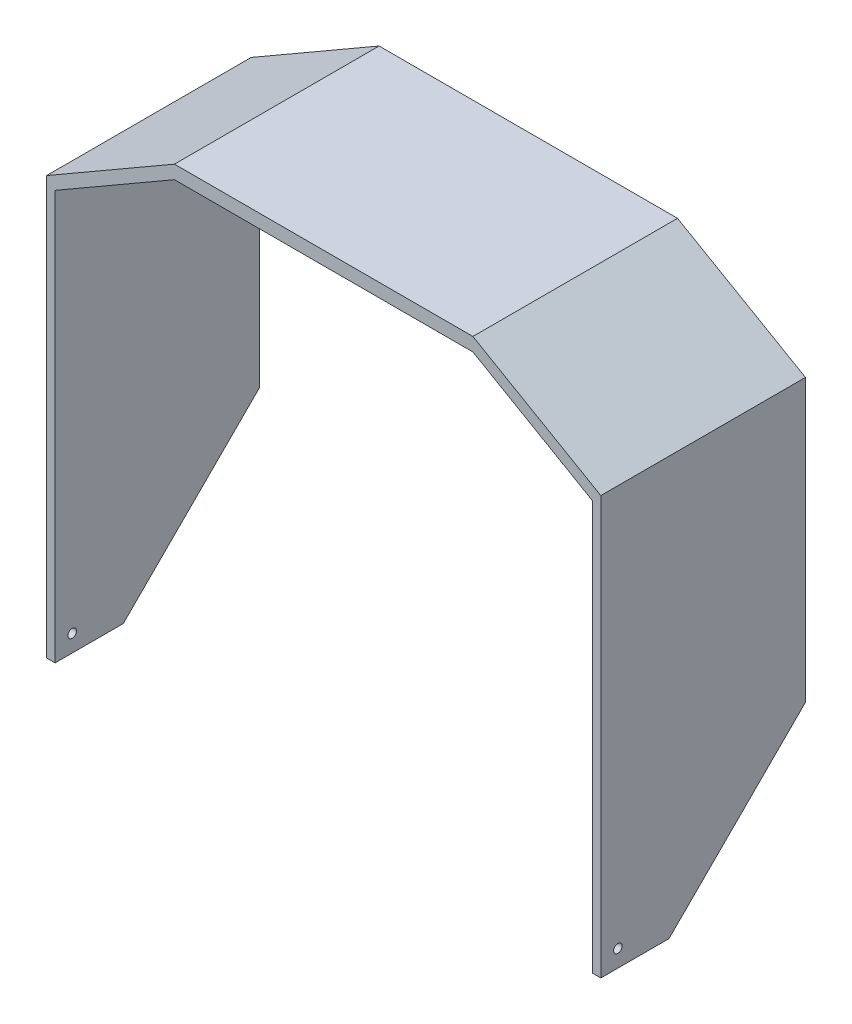
SolidWorks part; units mm, degrees
ref_plane "Front Plane" through (0, 0, 0) normal (0, 0, 1) x (1, 0, 0)
ref_plane "Top Plane" through (0, 0, 0) normal (0, 1, 0) x (1, 0, 0)
ref_plane "Right Plane" through (0, 0, 0) normal (1, 0, 0) x (0, 0, -1)
sketch "Sketch3" plane through (0, 0, 0) normal (0, 0, 1) x (1, 0, 0)
  line L0 (-5, 5) -> (-5, -240)
  line L2 (0, 0) -> (0, -240)
  line L4 (315, 0) -> (315, -240)
  line L6 (320, 5) -> (320, -240)
  line L7 (320, -240) -> (315, -240)
  line L8 (0, -240) -> (-5, -240)
  line L9 (0, 0) -> (70, 40.4145)
  line L10 (0, 0) -> (315, 0) construction
  line L11 (-5, 5) -> (320, 5) construction
  line L12 (70, 40.4145) -> (245, 40.4145)
  line L13 (245, 40.4145) -> (315, 0)
  line L14 (320, 5) -> (245, 48.3013)
  line L15 (245, 48.3013) -> (70, 48.3013)
  line L16 (70, 48.3013) -> (-5, 5)
  dimension "D1" = 315
  dimension "D2" = 240
  dimension "D4" = 120
  dimension "D5" = 120
  dimension "D6" = 70
  dimension "D7" = 120
  dimension "D8" = 120
  dimension "D3" = 5
extrude "Boss-Extrude2" add sketch "Sketch3" along normal blind 120
sketch "Sketch5" plane through (320, 0, 0) normal (1, 0, 0) x (0, 0, -1)
  line L0 (-120, -240) -> (0, -240) construction
  line L1 (-120, -240) -> (-120, 5) construction
  line L2 (-80, -240) -> (0, -160)
  line L3 (0, -240) -> (0, 5) construction
  line L4 (0, -160) -> (0, -240)
  line L5 (0, -240) -> (-80, -240)
  circle A0 centre (-110, -230) radius 2.5
  dimension "D1" = 10
  dimension "D3" = 5
  dimension "D2" = 10
  dimension "D4" = 80
extrude "Cut-Extrude2" cut sketch "Sketch5" against normal through all both and the other way through all
